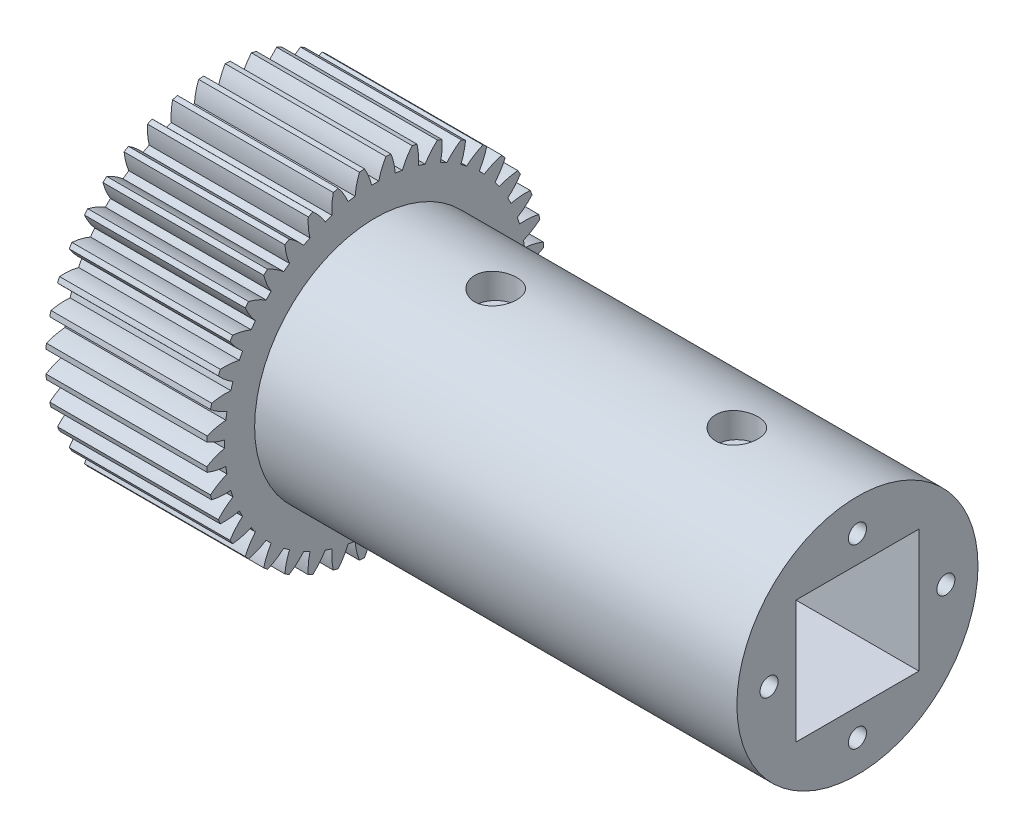
SolidWorks part; units mm, degrees
other "Markup1"
sketch "Sketch5" plane through (160, -41.9154, 41.9154) normal (0.985, -0.1562, 0.0735) x (0.1322, 0.9563, 0.2606)
ref_plane "Plane1" through (0, 0, 0) normal (0, 0, 1) x (1, 0, 0)
ref_plane "Plane2" through (0, 0, 0) normal (0, 1, 0) x (1, 0, 0)
ref_plane "Plane3" through (0, 0, 0) normal (1, 0, 0) x (0, 0, -1)
other "Configuration Table"
sketch "HoldingSke" plane through (0, 0, 0) normal (0, 1, 0) x (1, 0, 0)
  line L0 (0, 0) -> (0.383, -0.3214)
  line L1 (-15, 0) -> (100, 0) construction
  line L2 (0, 0) -> (-2.1039, 2.3779)
  line L3 (0, 0) -> (-11.863, 4.5341)
  line L4 (0, 0) -> (6.6156, 5.5511)
  line L5 (0, 0) -> (-46.8476, -17.4728)
  line L6 (0, 0) -> (-33.1585, -22.3721)
  line L7 (-2.1039, 2.3779) -> (8.6586, 51.2059)
  line L8 (-76.2, 54.61) -> (-76.1, 54.61)
  line L9 (-71.009, 38.7566) -> (-53.1078, 45.2721)
  line L10 (-76.2, 71.12) -> (104.1128, 71.12)
  line L11 (0, 0) -> (-40, 0)
  line L12 (-76.2, 101.6) -> (-76.133, 101.6)
  line L13 (24.9733, 27.94) -> (52.9518, 28.4284)
  line L14 (24.9733, 27.94) -> (24.9743, 27.94)
  line L15 (24.9733, 27.94) -> (100.4006, 29.5858)
  line L16 (-63.627, -2) -> (-12.827, -2)
  circle A0 centre (0, 0) radius 0.4
  circle A1 centre (0, 0) radius 37.499
  circle A2 centre (0, 0) radius 37.5
  circle A3 centre (0, 0) radius 0.4
  dimension "MHD" = 74.998
  dimension "Hub_dia" = 75
  dimension "Bore" = 0.8
  dimension "MBD" = 0.8
  dimension "Num_teeth" = 40
  dimension "Pitch" = 0.5
  dimension "Overall_len" = 50
  dimension "Show_teeth" = 40
  dimension "Thickness" = 40
  dimension "OAL" = 50.0001
  dimension "T_dim" = 0.1
  dimension "Ap" = 20
  dimension "H" = 19.05
  dimension "Pitch_radius" = 180.3128
  dimension "Width" = 40
  dimension "Backlash" = 0.067
  dimension "Addendum_fac" = 1
  dimension "Dedendum_fac" = 1.25
  dimension "Clearance_fac" = 0.25
  dimension "Dedendum_add" = 0.001
  dimension "Module" = 2
sketch "BasProSke" plane through (0, 0, 0) normal (0, 1, 0) x (1, 0, 0)
  line L0 (-10, 0) -> (60, 0) construction
  line L1 (0, 0) -> (0, 42)
  line L2 (0, 0) -> (40, 0)
  line L3 (40, 0) -> (40, 42)
  line L4 (40, 42) -> (0, 42)
  dimension "Thickness" = 40
  dimension "Diameter" = 84
revolve "Base-Revolve" add sketch "BasProSke" angle 360 about L0
sketch "TooCutSke" plane through (0, 0, 0) normal (1, 0, 0) x (0, 0, -1)
  line L1 (0, 0) -> (0, 107) construction
  line L2 (0, 0) -> (-1.6876, 39.9644) construction
  line L3 (0, 0) -> (-6.2726, 79.7007) construction
  line L4 (-1.6876, 39.9644) -> (-3.1363, 39.8504) construction
  arc A0 (0.8828, 37.4886) -> (-0.8828, 37.4886) centre (0, 0) ccw
  arc A1 (2.6784, 41.94) -> (-2.6784, 41.94) centre (0, 0) ccw
  circle A2 centre (0, 0) radius 40 construction
  circle A3 centre (0, 0) radius 37.5877 construction
  arc A4 (-0.8828, 37.4886) -> (-2.6784, 41.94) centre (-16.451, 33.7965) ccw
  arc A5 (2.6784, 41.94) -> (0.8828, 37.4886) centre (16.451, 33.7965) ccw
  dimension "Root_dia" = 74.998
  dimension "Overcut_dia" = 84.0508
  dimension "Pitch_dia" = 80
  dimension "Base_dia" = 75.1754
  dimension "Flank_rad" = 16
  dimension "Half_ang" = 4.5
  dimension "Half_CT" = 1.4531
extrude "ToothCut" cut sketch "TooCutSke" along normal through all
fillet "Breaks" [suppressed] radius 0.04 tangent propagation no
fillet "RootFillets" [suppressed] radius 0.501
pattern_circular "TeethCuts" count 40 every 9 about axis through (-10, 0, 0) along (1, 0, 0) of "ToothCut", "RootFillets", "Breaks"
sketch "HubNeaOneSke" plane through (0, 0, 0) normal (-1, 0, 0) x (0, 0, 1)
  circle A0 centre (0, 0) radius 37.499
  dimension "Diameter" = 74.998
extrude "HubNearOne" [suppressed] add sketch "HubNeaOneSke" along normal blind 10.0001
sketch "HubNeaBotSke" plane through (0, 0, 0) normal (-1, 0, 0) x (0, 0, 1)
  circle A0 centre (0, 0) radius 37.499
  dimension "Diameter" = 74.998
extrude "HubNearBoth" [suppressed] add sketch "HubNeaBotSke" along normal blind 5
ref_plane "FarPln" through (40, 0, 0) normal (1, 0, 0) x (0, 0, -1)
sketch "HubFarSke" plane through (40, 0, 0) normal (1, 0, 0) x (0, 0, -1)
  circle A0 centre (0, 0) radius 37.499
  dimension "Diameter" = 74.998
extrude "HubFar" [suppressed] add sketch "HubFarSke" along normal blind 5
sketch "BorSke" plane through (0, 0, 0) normal (1, 0, 0) x (0, 0, -1)
  circle A0 centre (0, 0) radius 0.4
  dimension "Diameter" = 0.8
extrude "Bore" cut sketch "BorSke" along normal mid plane 100.0001
sketch "KeySke" plane through (0, 0, 0) normal (1, 0, 0) x (0, 0, -1)
  line L0 (-0.05, 0) -> (-0.05, 0.5)
  line L1 (-0.05, 0.5) -> (0.05, 0.5)
  line L2 (0.05, 0.5) -> (0.05, 0)
  line L3 (0, 0) -> (0, 34) construction
  line L4 (-0.05, 0) -> (0.05, 0)
  dimension "Offset" = 0.5
extrude "Keyway" [suppressed] cut sketch "KeySke" along normal mid plane 100.0001
pattern_circular "Keyway2" [suppressed] count 2 every 90 about axis through (-10, 0, 0) along (1, 0, 0) reverse direction yes
sketch "Sketch1" plane through (40, 0, 0) normal (1, 0, 0) x (0, 0, -1)
  line L1 (15.3, 15.3) -> (-15.3, 15.3)
  line L2 (15.3, 15.3) -> (15.3, -15.3)
  line L3 (15.3, -15.3) -> (-15.3, -15.3)
  line L4 (-15.3, 15.3) -> (-15.3, -15.3)
  line L5 (15.3, 15.3) -> (-15.3, -15.3) construction
  line L6 (15.3, -15.3) -> (-15.3, 15.3) construction
  point P0 (0, 0)
  dimension "D1" = 30.6
extrude "Cut-Extrude1" cut sketch "Sketch1" against normal through all
sketch "Sketch2" plane through (40, 0, 0) normal (1, 0, 0) x (0, 0, -1)
  line L0 (-15.3, -15.3) -> (15.3, -15.3) construction
  line L1 (15.3, -15.3) -> (15.3, 15.3) construction
  line L2 (15.3, 15.3) -> (-15.3, 15.3) construction
  line L3 (-15.3, 15.3) -> (-15.3, -15.3) construction
  line L4 (-15.3, -15.3) -> (15.3, -15.3)
  line L5 (15.3, -15.3) -> (15.3, 15.3)
  line L6 (15.3, 15.3) -> (-15.3, 15.3)
  line L7 (-15.3, 15.3) -> (-15.3, -15.3)
  circle A0 centre (0, 0) radius 30
  dimension "D1" = 60
extrude "Boss-Extrude1" add sketch "Sketch2" along normal blind 120
sketch "Sketch3" plane through (160, 0, 0) normal (1, 0, 0) x (0, 0, -1)
  line L0 (0, 0) -> (22, 0) construction
  circle A0 centre (22, 0) radius 2.25
  circle A1 centre (0, -22) radius 2.25
  circle A2 centre (-22, 0) radius 2.25
  circle A3 centre (0, 22) radius 2.25
  point P13 (0, 0)
  dimension "D2" = 4.5
  dimension "D1" = 22
  dimension "D3" = 4
extrude "Cut-Extrude2" cut sketch "Sketch3" against normal blind 10
ref_plane "Mid Plane" through (100, 0, 0) normal (1, 0, 0) x (0, 0, -1)
sketch "Sketch4" plane through (0, 0, 0) normal (0, 1, 0) x (1, 0, 0)
  line L0 (160, 0) -> (40, 0) construction
  line L1 (160, -30) -> (160, 30) construction
  line L2 (40, -30) -> (40, 30) construction
  circle A0 centre (70, 0) radius 3.2
  circle A1 centre (130, 0) radius 3.2
  point P4 (70, 0)
  point P7 (0, 0)
  point P8 (100, 0)
  point P10 (130, 0)
  dimension "D3" = 6.4
  dimension "D1" = 30
  dimension "D2" = 30
extrude "Cut-Extrude3" cut sketch "Sketch4" against normal through all both and the other way through all
ref_plane "Plane5" through (0, -30, 0) normal (0, -1, 0) x (-1, 0, 0)
sketch "Sketch6" plane through (0, -30, 0) normal (0, -1, 0) x (-1, 0, 0)
  line L1 (-123.9956, 0) -> (-126.9978, 5.2)
  line L2 (-126.9978, 5.2) -> (-133.0022, 5.2)
  line L3 (-133.0022, 5.2) -> (-136.0044, 0)
  line L4 (-136.0044, 0) -> (-133.0022, -5.2)
  line L5 (-133.0022, -5.2) -> (-126.9978, -5.2)
  line L6 (-126.9978, -5.2) -> (-123.9956, 0)
  line L7 (-76.0044, 0) -> (-73.0022, -5.2)
  line L8 (-73.0022, -5.2) -> (-66.9978, -5.2)
  line L9 (-66.9978, -5.2) -> (-63.9956, 0)
  line L10 (-63.9956, 0) -> (-66.9978, 5.2)
  line L11 (-66.9978, 5.2) -> (-73.0022, 5.2)
  line L12 (-73.0022, 5.2) -> (-76.0044, 0)
  circle A0 centre (-130, 0) radius 5.2 construction
  circle A1 centre (-70, 0) radius 5.2 construction
  dimension "D1" = 10.4
extrude "Cut-Extrude4" cut sketch "Sketch6" against normal blind 10
ref_plane "Plane6" through (0, 30, 0) normal (0, 1, 0) x (1, 0, 0)
sketch "Sketch7" plane through (0, 30, 0) normal (0, 1, 0) x (1, 0, 0)
  circle A0 centre (70, 0) radius 5.25
  circle A1 centre (130, 0) radius 5.25
  dimension "D1" = 10.5
  dimension "D2" = 10.5
extrude "Cut-Extrude5" cut sketch "Sketch7" against normal blind 6.5
equation "' \"Module@HoldingSke\" = 6.35"
equation "' \"Num_teeth@HoldingSke\" = 12"
equation "' \"Ap@HoldingSke\" =  20"
equation "' \"Ap@HoldingSke\" = 20"
equation "' \"Width@HoldingSke\" = 0.5 * 25.4"
equation "' \"Hub_dia@HoldingSke\"= 1 * 25.4"
equation "' \"Hub_dia@HoldingSke\" = 1 * 25.4"
equation "' \"Overall_len@HoldingSke\" = 1.0 * 25.4"
equation "' \"Bore@HoldingSke\" = 0.75 * 25.4"
equation "' \"T_dim@HoldingSke\" = 0.1 * 25.4"
equation "' \"Width@KeySke\" = 0.25 * 25.4"
equation "' \"Show_teeth@HoldingSke\" = 13"
equation "' \"Backlash@HoldingSke\" = 0.009 * 25.4"
equation "' \"Addendum_fac@HoldingSke\" = 1.0"
equation "' \"Dedendum_fac@HoldingSke\" = 1.25"
equation "' \"Dedendum_add@HoldingSke\" = 0.00005 * 25.4"
equation "' \"Clearance_fac@HoldingSke\" = 0.25"
equation "\"Pitch@HoldingSke\" = 1 / \"Module@HoldingSke\""
equation "\"Overcut_dia@TooCutSke\" = (\"Num_teeth@HoldingSke\" + 2 * \"Addendum_fac@HoldingSke\") / \"Pitch@HoldingSke\" + 0.002 * 25.4"
equation "\"Pitch_dia@TooCutSke\" = \"Num_teeth@HoldingSke\" / \"Pitch@HoldingSke\""
equation "\"Base_dia@TooCutSke\" = \"Num_teeth@HoldingSke\" / \"Pitch@HoldingSke\" * cos((\"Ap@HoldingSke\"  * 3.14159265 / 180))"
equation "\"Root_dia@TooCutSke\" = (\"Num_teeth@HoldingSke\" + 2) / \"Pitch@HoldingSke\" - 2 * (\"Addendum_fac@HoldingSke\" + \"Dedendum_fac@HoldingSke\") / \"Pitch@HoldingSke\" - \"Dedendum_add@HoldingSke\" * 2"
equation "\"Half_ang@TooCutSke\" = 180 / \"Num_teeth@HoldingSke\""
equation "\"Half_CT@TooCutSke\" = \"Num_teeth@HoldingSke\" / \"Pitch@HoldingSke\" * sin((3.14159265 / 2 / \"Num_teeth@HoldingSke\")) / 2 - 7 * \"Backlash@HoldingSke\" / 4"
equation "\"Flank_rad@TooCutSke\" = \"Num_teeth@HoldingSke\" / \"Pitch@HoldingSke\" / 5"
equation "\"Radius@RootFillets\" = \"Clearance_fac@HoldingSke\" / \"Pitch@HoldingSke\" + \"Dedendum_add@HoldingSke\""
equation "\"Break_rad@Breaks\" = 0.02 / \"Pitch@HoldingSke\""
equation "\"Thickness@HoldingSke\" = \"Width@HoldingSke\""
equation "\"OAL@HoldingSke\" = \"Thickness@HoldingSke\""
equation "\"MHD@HoldingSke\" = (\"Num_teeth@HoldingSke\" + 2) / \"Pitch@HoldingSke\" - 2 * (\"Addendum_fac@HoldingSke\" + \"Dedendum_fac@HoldingSke\")  / \"Pitch@HoldingSke\" - \"Dedendum_add@HoldingSke\" * 2"
equation "\"MBD@HoldingSke\" = (\"Num_teeth@HoldingSke\" + 2) / \"Pitch@HoldingSke\" - 2 * (\"Addendum_fac@HoldingSke\" + \"Dedendum_fac@HoldingSke\")  / \"Pitch@HoldingSke\" - \"Dedendum_add@HoldingSke\" * 2 - 0.002 * 25.4"
equation "\"MHD@HoldingSke\" = ((sgn( \"MHD@HoldingSke\" - \"Hub_dia@HoldingSke\" )-1)*( \"MHD@HoldingSke\" - \"Hub_dia@HoldingSke\" ))/-2+ \"Hub_dia@HoldingSke\""
equation "\"MBD@HoldingSke\" = ((sgn( \"MBD@HoldingSke\" - \"Bore@HoldingSke\" )-1)*( \"MBD@HoldingSke\" - \"Bore@HoldingSke\" ))/-2+ \"Bore@HoldingSke\""
equation "\"OAL@HoldingSke\" = ((sgn( \"OAL@HoldingSke\" - \"Overall_len@HoldingSke\" )+1)*( \"OAL@HoldingSke\" - \"Overall_len@HoldingSke\" ))/2 + \"Overall_len@HoldingSke\" + 0.000002 * 25.4"
equation "\"Num_teeth@TeethCuts\" = int( \"Show_teeth@HoldingSke\" ) + 1"
equation "\"Num_teeth@TeethCuts\" = ((sgn( \"Num_teeth@TeethCuts\" - \"Num_teeth@HoldingSke\" )-1)*( \"Num_teeth@TeethCuts\" - \"Num_teeth@HoldingSke\" ))/-2+ \"Num_teeth@HoldingSke\""
equation "\"Num_teeth@TeethCuts\" = ((sgn( \"Num_teeth@TeethCuts\" - 2.0)+1)*( \"Num_teeth@TeethCuts\" - 2.0))/2 +2.0"
equation "\"Angle@TeethCuts\" = 360.0 / \"Num_teeth@HoldingSke\""
equation "\"Diameter@BasProSke\" = (\"Num_teeth@HoldingSke\" + 2 * \"Addendum_fac@HoldingSke\") / \"Pitch@HoldingSke\""
equation "\"Thickness@BasProSke\"  = \"Thickness@HoldingSke\""
equation "' \"Fillet_rad@BasProSke\" =  \"Thickness@HoldingSke\" * 0.05"
equation "' \"Fillet_rad@BasProSke\" = \"Thickness@HoldingSke\" * 0.05"
equation "\"MHD@HoldingSke\" = ((sgn( \"MHD@HoldingSke\" - \"Root_dia@TooCutSke\" )-1)*( \"MHD@HoldingSke\" - \"Root_dia@TooCutSke\" ))/-2+ \"Root_dia@TooCutSke\""
equation "\"Diameter@HubNeaOneSke\" = \"MHD@HoldingSke\""
equation "\"Length@HubNearOne\" = \"OAL@HoldingSke\" - \"Thickness@BasProSke\""
equation "\"Diameter@HubNeaBotSke\" = \"MHD@HoldingSke\""
equation "\"Length@HubNearBoth\" = ( \"OAL@HoldingSke\" - \"Thickness@BasProSke\" ) / 2.0"
equation "\"Thickness@FarPln\" = \"Thickness@BasProSke\""
equation "\"Diameter@HubFarSke\" = \"MHD@HoldingSke\""
equation "\"Length@HubFar\" = ( \"OAL@HoldingSke\" - \"Thickness@BasProSke\" ) / 2.0"
equation "\"Diameter@BorSke\" = \"MBD@HoldingSke\""
equation "\"D1@Bore\" = \"OAL@HoldingSke\" * 2.0"
equation "\"D1@Keyway\" = \"OAL@HoldingSke\" * 2.0"
equation "\"Offset@KeySke\" = \"T_dim@HoldingSke\" + \"MBD@HoldingSke\" / 2.0"
equation "\"D2@Sketch4\"=\"D1@Sketch4\""
